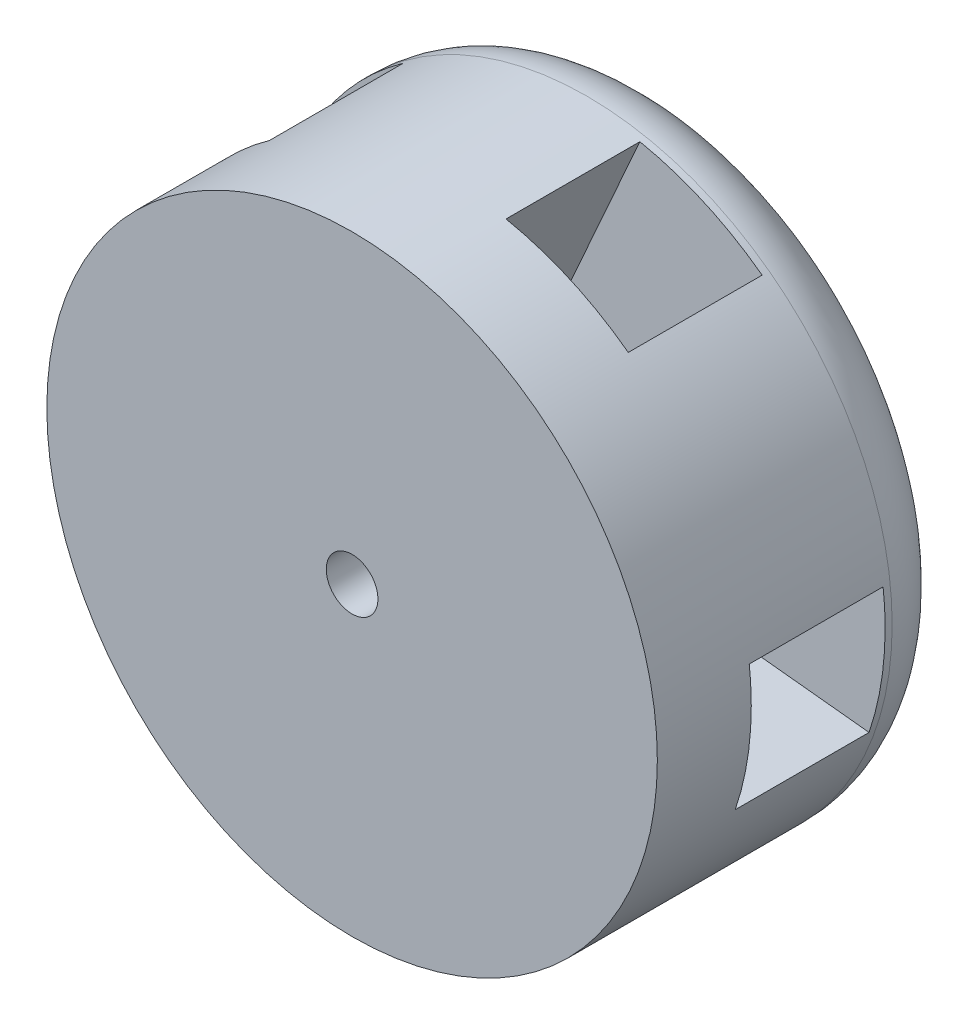
SolidWorks part; units mm, degrees
note: '?' marks a value the reader was unsure of. The reader was unsure of these and kept them because the rebuilt part matched: shared geometry of "Sketch1<4>".
ref_plane "Front Plane" through (0, 0, 0) normal (0, 0, 1) x (1, 0, 0)
ref_plane "Top Plane" through (0, 0, 0) normal (0, 1, 0) x (1, 0, 0)
ref_plane "Right Plane" through (0, 0, 0) normal (1, 0, 0) x (0, 0, -1)
sketch "Sketch1" plane through (0, 0, 0) normal (0, 0, 1) x (1, 0, 0)
  line L0 (-1.1, 0) -> (1.1, 0) construction
  line L2 (0, 0) -> (-0.7778, -0.7778) construction
  line L6 (0, 0) -> (0.7778, -0.7778) construction
  circle A0 centre (0, 0) radius 13
  circle A1 centre (0, 0) radius 1.1
  dimension "D1" = 2.2
  dimension "D2" = 26
  dimension "D3" = 45
extrude "Boss-Extrude1" add sketch "Sketch1" along normal blind 10
extrude "Boss-Extrude2" add sketch "Sketch1<4>" against normal blind 3
sketch "Sketch1<4>" plane through (0, 0, 0) normal (0, 0, 1) x (1, 0, 0) same geometry as "Sketch1"
ref_plane "Plane1" through (0, 0, 7) normal (0, 0, -1) x (-1, 0, 0)
sketch "Sketch2" plane through (0, 0, 7) normal (0, 0, -1) x (-1, 0, 0)
  line L0 (0, 0) -> (0, -13)
  line L1 (-12.2328, 4.3999) -> (0, 0)
  line L2 (0, 0) -> (9.9268, 8.394)
  line L3 (0, 13) -> (0, -13) construction
  circle A0 centre (0, 0) radius 13 construction
  circle A1 centre (0, 0) radius 13
  dimension "D1" = 109.782
  dimension "D2" = 120
ref_plane "Plane3" through (-11.2583, -6.5, 0) normal (-0.866, -0.5, 0) x (0, 0, -1)
sketch "Sketch4" plane through (-11.2864, -6.4513, 0) normal (0.866, 0.5, 0) x (0.5, -0.866, 0)
  line L0 (10.9055, 0) -> (7.2526, 0) construction
  line L1 (2.9062, -0.3) -> (-2.7938, -0.3)
  line L2 (2.9062, -0.3) -> (2.9062, -6)
  line L3 (2.9062, -6) -> (-2.7938, -6)
  line L4 (-2.7938, -0.3) -> (-2.7938, -6)
  line L5 (10.9055, 0) -> (7.2526, 0)
  line L6 (13.0562, 3) -> (-12.9438, 3) construction
  line L7 (13.0562, 3) -> (-12.9438, 3)
  line L8 (0.0562, 5) -> (0.0562, -19.3981) construction
  point P10 (0.0562, -0.3)
  dimension "D1" = 5.7
  dimension "D2" = 5.7
  dimension "D3" = 6
ref_axis "Eix de revolució" through (0, 0, 10) along (0, 0, -1)?
fillet "Fillet1" radius 3 1 edges at (13, 0, -3) type face fillet first side face at (13, 0, -3) second side face at (13, 0, 10)
extrude "Cut-Extrude1" cut sketch "Sketch4" along normal blind 9 contours L4 L3 L2 L1
pattern_circular "CirPattern1" count 5 over 360 about axis through (0, 0, 0) along (0, 0, 1) of "Cut-Extrude1"
hole_wizard "CSK for M3 Oval Head Machine Screw1" positions "Sketch15" profile "Sketch13" countersink size "M3" standard "ANSI Metric"
sketch "Sketch15" plane through (-5.7778, 0, 0) normal (-1, 0, 0) x (0, 0, 1)
  point P0 (6.0161, -18.3217)
sketch "Sketch13" plane through (-5.7778, -18.3217, 6.0161) normal (0, 1, 0) x (0, 0, 1)
  line L0 (0, 0) -> (0, 18.7778)
  line L1 (0, 18.7778) -> (1.8, 18.7778)
  line L2 (1.8, 18.7778) -> (1.8, 1.35)
  line L3 (1.8, 1.35) -> (3.15, 0)
  line L5 (3.15, 0) -> (0, 0)
  line L6 (-1.8, 1.35) -> (-3.15, 0) construction
  line L11 (0, -6.35) -> (0, 107.95) construction
  dimension "Thru Hole Dia." = 3.6
  dimension "Thru Hole Depth" = 18.7778
  dimension "Near C'Sink Dia." = 6.3
  dimension "Near C'Sink Angle" = 90
